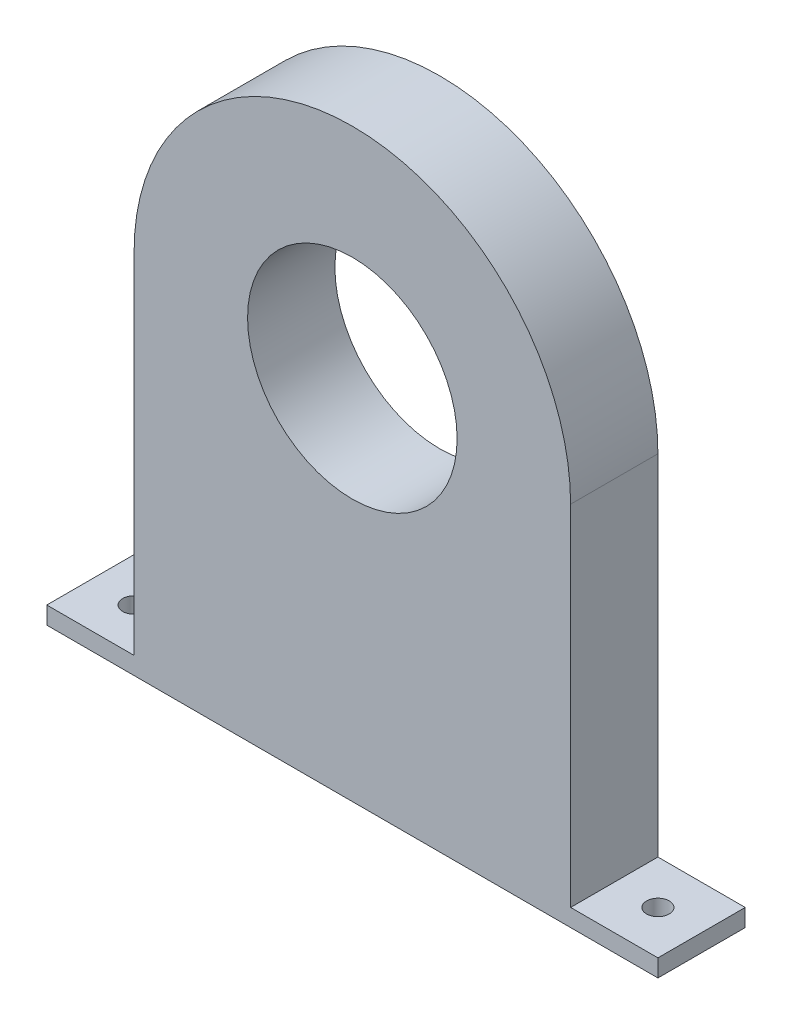
SolidWorks part; units mm, degrees
ref_plane "Front Plane" through (0, 0, 0) normal (0, 0, 1) x (1, 0, 0)
ref_plane "Top Plane" through (0, 0, 0) normal (0, 1, 0) x (1, 0, 0)
ref_plane "Right Plane" through (0, 0, 0) normal (1, 0, 0) x (0, 0, -1)
sketch "Sketch1" plane through (0, 0, 0) normal (0, 1, 0) x (1, 0, 0)
  line L1 (44.45, 6.35) -> (-44.45, 6.35)
  line L2 (44.45, 6.35) -> (44.45, -6.35)
  line L3 (44.45, -6.35) -> (-44.45, -6.35)
  line L4 (-44.45, 6.35) -> (-44.45, -6.35)
  line L5 (44.45, 6.35) -> (-44.45, -6.35) construction
  line L6 (44.45, -6.35) -> (-44.45, 6.35) construction
  line L7 (-38.1, 0) -> (-44.45, 0) construction
  line L8 (38.1, 0) -> (44.45, 0) construction
  circle A0 centre (-38.1, 0) radius 1.651
  circle A1 centre (38.1, 0) radius 1.651
  point P0 (0, 0)
  dimension "D1" = 3.302
  dimension "D2" = 76.2
  dimension "D3" = 88.9
  dimension "D4" = 12.7
extrude "Boss-Extrude1" add sketch "Sketch1" along normal blind 2.54
sketch "Sketch2" plane through (0, 2.54, 0) normal (0, 1, 0) x (1, 0, 0)
  line L0 (44.45, 6.35) -> (-44.45, 6.35) construction
  line L1 (31.75, 6.35) -> (-31.75, 6.35)
  line L2 (31.75, 6.35) -> (31.75, -6.35)
  line L3 (31.75, -6.35) -> (-31.75, -6.35)
  line L4 (-31.75, 6.35) -> (-31.75, -6.35)
  line L5 (31.75, 6.35) -> (-31.75, -6.35) construction
  line L6 (31.75, -6.35) -> (-31.75, 6.35) construction
  point P0 (0, 0)
  dimension "D1" = 63.5
extrude "Boss-Extrude2" add sketch "Sketch2" along normal blind 50.8
sketch "Sketch3" plane through (0, 0, 6.35) normal (0, 0, 1) x (1, 0, 0)
  line L0 (31.75, 53.34) -> (-31.75, 53.34)
  arc A0 (31.75, 53.34) -> (-31.75, 53.34) centre (0, 53.34) ccw
extrude "Boss-Extrude3" add sketch "Sketch3" against normal up to surface (12.7 mm away) contours A0 L0 up to face at (0, 14.605, -6.35)
sketch "Sketch4" plane through (0, 0, -6.35) normal (0, 0, -1) x (-1, 0, 0)
  line L0 (0, 53.34) -> (0, 0) construction
  line L1 (-44.45, 0) -> (44.45, 0) construction
  circle A0 centre (0, 53.34) radius 15.24
  dimension "D1" = 30.48
extrude "Cut-Extrude1" cut sketch "Sketch4" against normal up to surface (12.7 mm away) up to face at (0, 18.5738, 6.35)
